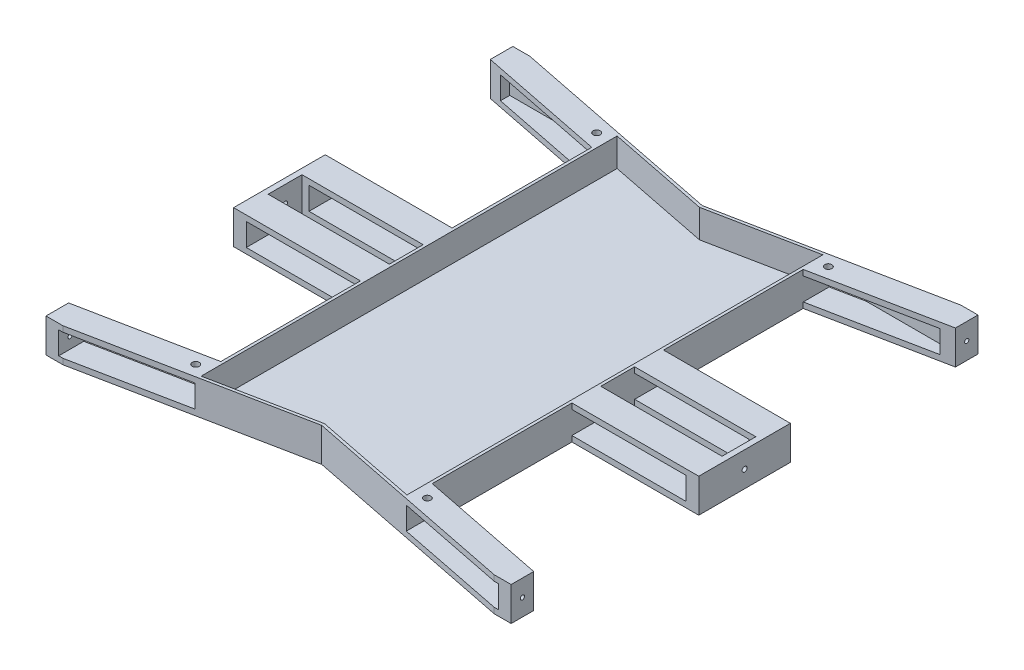
SolidWorks part; units mm, degrees
ref_plane "Front Plane" through (0, 0, 0) normal (0, 0, 1) x (1, 0, 0)
ref_plane "Top Plane" through (0, 0, 0) normal (0, 1, 0) x (1, 0, 0)
ref_plane "Right Plane" through (0, 0, 0) normal (1, 0, 0) x (0, 0, -1)
sketch "Sketch1" plane through (0, 0, 0) normal (0, 1, 0) x (1, 0, 0)
  line L1 (-55, 0) -> (55, 0) construction
  line L2 (165, 32.5) -> (165, -32.5)
  line L3 (165, -32.5) -> (75, -32.5)
  line L4 (75, -32.5) -> (75, -131.6)
  line L5 (75, -131.6) -> (165, -149.6)
  line L6 (165, -149.6) -> (165, -165.6)
  line L7 (165, -165.6) -> (153, -165.6)
  line L8 (153, -165.6) -> (0, -135)
  line L9 (0, -55) -> (0, 55) construction
  line L11 (-165, 32.5) -> (-165, -32.5)
  line L12 (-165, -32.5) -> (-75, -32.5)
  line L13 (-75, -32.5) -> (-75, -131.6)
  line L14 (-75, -131.6) -> (-165, -149.6)
  line L15 (-165, -149.6) -> (-165, -165.6)
  line L16 (-165, -165.6) -> (-153, -165.6)
  line L17 (-153, -165.6) -> (0, -135)
  line L18 (165, 32.5) -> (75, 32.5)
  line L19 (75, 32.5) -> (75, 131.6)
  line L20 (165, 165.6) -> (153, 165.6)
  line L21 (165, 149.6) -> (165, 165.6)
  line L22 (75, 131.6) -> (165, 149.6)
  line L23 (153, 165.6) -> (0, 135)
  line L24 (-165, 149.6) -> (-165, 165.6)
  line L25 (-165, 165.6) -> (-153, 165.6)
  line L26 (-153, 165.6) -> (0, 135)
  line L27 (-75, 131.6) -> (-165, 149.6)
  line L28 (-165, 32.5) -> (-75, 32.5)
  line L29 (-75, 32.5) -> (-75, 131.6)
  line L30 (75, -131.6) -> (75, -150) construction
  line L32 (-75, -131.6) -> (-75, -150) construction
  line L34 (-75, 131.6) -> (-75, 150) construction
  line L36 (75, 131.6) -> (75, 150) construction
  point P21 (165, 0)
  point P33 (-165, 0)
  dimension "D1" = 300
  dimension "D2" = 270
  dimension "D3" = 150
  dimension "D4" = 16
  dimension "D5" = 12
  dimension "D6" = 65
  dimension "D7" = 90
extrude "Boss-Extrude1" add sketch "Sketch1" along normal blind 12 and the other way blind 12
sketch "Sketch2" plane through (0, 0, 165.6) normal (0, 0, 1) x (1, 0, 0)
  line L1 (-156, -8) -> (156, -8)
  line L2 (-156, -8) -> (-156, 8)
  line L3 (-156, 8) -> (156, 8)
  line L4 (156, -8) -> (156, 8)
  line L7 (55, 0) -> (-55, 0) construction
  dimension "D1" = 8
  dimension "D2" = 8
  dimension "D3" = 156
  dimension "D4" = 156
extrude "Cut-Extrude1" cut sketch "Sketch2" against normal blind 320
sketch "Sketch4" plane through (0, 12, 0) normal (0, 1, 0) x (1, 0, 0)
  line L0 (-55, 0) -> (55, 0) construction
  line L1 (-161, 12) -> (-75, 12)
  line L2 (-161, 12) -> (-161, -12)
  line L3 (-161, -12) -> (-75, -12)
  line L4 (-75, 12) -> (-75, -12)
  line L5 (-165, 32.5) -> (-165, -32.5) construction
  line L6 (-75, -32.5) -> (-75, -131.6) construction
  line L7 (0, -55) -> (0, 55) construction
  line L8 (161, -12) -> (75, -12)
  line L9 (75, 12) -> (75, -12)
  line L10 (161, 12) -> (75, 12)
  line L11 (161, 12) -> (161, -12)
  dimension "D1" = 12
  dimension "D2" = 12
  dimension "D3" = 4
extrude "Cut-Extrude2" cut sketch "Sketch4" against normal blind 24
sketch "Sketch6" plane through (0, 0, 0) normal (1, 0, 0) x (0, 0, -1)
  line L0 (-149.6, 0) -> (-165.6, 0) construction
  line L1 (149.6, 0) -> (165.6, 0) construction
  circle A0 centre (-157.6, 0) radius 1.5
  circle A1 centre (157.6, 0) radius 1.5
  point P6 (-157.6, 0)
  point P10 (157.6, 0)
  dimension "D1" = 3
extrude "Cut-Extrude3" cut sketch "Sketch6" against normal through all both and the other way through all
sketch "Sketch7" plane through (165, 0, 0) normal (1, 0, 0) x (0, 0, -1)
  circle A0 centre (0, 0) radius 1.75
  dimension "D1" = 3.5
extrude "Cut-Extrude4" cut sketch "Sketch7" against normal up to surface (330 mm away) up to face at (-165, 0, 0)
sketch "Sketch8" plane through (0, 12, 0) normal (0, 1, 0) x (1, 0, 0)
  line L0 (0, 135) -> (0, -135) construction
  line L1 (156, -12) -> (156, 12) construction
  line L2 (156, 8) -> (144, 8)
  line L3 (156, 8) -> (156, -8)
  line L4 (156, -8) -> (144, -8)
  line L5 (144, 8) -> (144, -8)
  line L6 (-156, 0) -> (165, 0) construction
  line L7 (-156, 12) -> (-156, -12) construction
  line L8 (165, -32.5) -> (165, 32.5) construction
  line L9 (-156, -8) -> (-144, -8)
  line L10 (-144, 8) -> (-144, -8)
  line L11 (-156, 8) -> (-144, 8)
  line L12 (-156, 8) -> (-156, -8)
  point P16 (144, 0)
  dimension "D1" = 16
  dimension "D2" = 12
extrude "Cut-Extrude5" [suppressed] cut sketch "Sketch8" against normal up to surface (5 mm away) up to face at (0, 8, 1.3176)
sketch "Sketch11" plane through (0, 12, 0) normal (0, 1, 0) x (1, 0, 0)
  line L0 (-75, -150) -> (-75, 150)
  line L1 (-153, -165.6) -> (0, -135) construction
  line L2 (0, 135) -> (-153, 165.6) construction
  line L3 (75, 150) -> (75, -150)
  line L4 (153, 165.6) -> (0, 135) construction
  line L5 (0, -135) -> (153, -165.6) construction
  line L6 (75, 32.5) -> (75, 131.6) construction
  line L7 (-75, 131.6) -> (-75, 32.5) construction
  line L8 (0, -135) -> (75, -150)
  line L9 (-75, -150) -> (0, -135)
  line L10 (0, 135) -> (-75, 150)
  line L11 (75, 150) -> (0, 135)
extrude "Cut-Extrude7" cut sketch "Sketch11" against normal up to surface (4 mm away) up to face at (0, 8, 1.3176)
sketch "Sketch12" plane through (0, -8, 0) normal (0, 1, 0) x (1, 0, 0)
  line L0 (-75, 150) -> (-75, -150)
  line L1 (-153, -165.6) -> (0, -135) construction
  line L2 (75, 150) -> (75, -150)
  line L3 (-75, -150) -> (0, -135)
  line L4 (0, -135) -> (75, -150)
  line L5 (-75, 150) -> (0, 135)
  line L6 (0, 135) -> (75, 150)
  line L7 (0, 132.9604) -> (73, 147.5604)
  line L8 (73, 147.5604) -> (73, -147.5604)
  line L9 (0, -132.9604) -> (73, -147.5604)
  line L10 (-73, -147.5604) -> (0, -132.9604)
  line L11 (-73, 147.5604) -> (-73, -147.5604)
  line L12 (-73, 147.5604) -> (0, 132.9604)
  dimension "D1" = 2
extrude "Boss-Extrude2" add sketch "Sketch12" along normal blind 20
sketch "Sketch14" plane through (0, 12, 0) normal (0, 1, 0) x (1, 0, 0)
  line L0 (0, 135) -> (0, -135) construction
  line L1 (75, 0) -> (-75, 0) construction
  line L2 (75, -12) -> (75, 12) construction
  line L3 (-75, 12) -> (-75, -12) construction
  line L4 (-83.9461, 133.3892) -> (-80.4076, 151.0815) construction
  line L5 (-165, 149.6) -> (-75, 131.6) construction
  line L6 (0, 135) -> (-153, 165.6) construction
  circle A0 centre (-82.1768, 142.2354) radius 2.5
  circle A1 centre (82.1768, 142.2354) radius 2.5
  circle A2 centre (82.1768, -142.2354) radius 2.5
  circle A3 centre (-82.1768, -142.2354) radius 2.5
  dimension "D2" = 5
  dimension "D1" = 82
extrude "Cut-Extrude8" cut sketch "Sketch14" against normal up to next
equation "\"A\"= 4"
equation "\"D1@Boss-Extrude1\"=3*\"A\""
equation "\"D2@Boss-Extrude1\"=3*\"A\""
equation "\"D1@Sketch2\"=2*\"A\""
equation "\"D2@Sketch2\"=2*\"A\""
equation "\"D1@Sketch4\"=3*\"A\""
equation "\"D2@Sketch4\"=3*\"A\""
equation "\"D3@Sketch4\"=\"A\""
equation "\"D1@Cut-Extrude2\"=6*\"A\""
equation "\"D1@Cut-Extrude1\"=80*\"A\""
equation "\"D3@Sketch2\"=\"A\" * 39"
equation "\"D4@Sketch2\"=\"A\" * 39"
